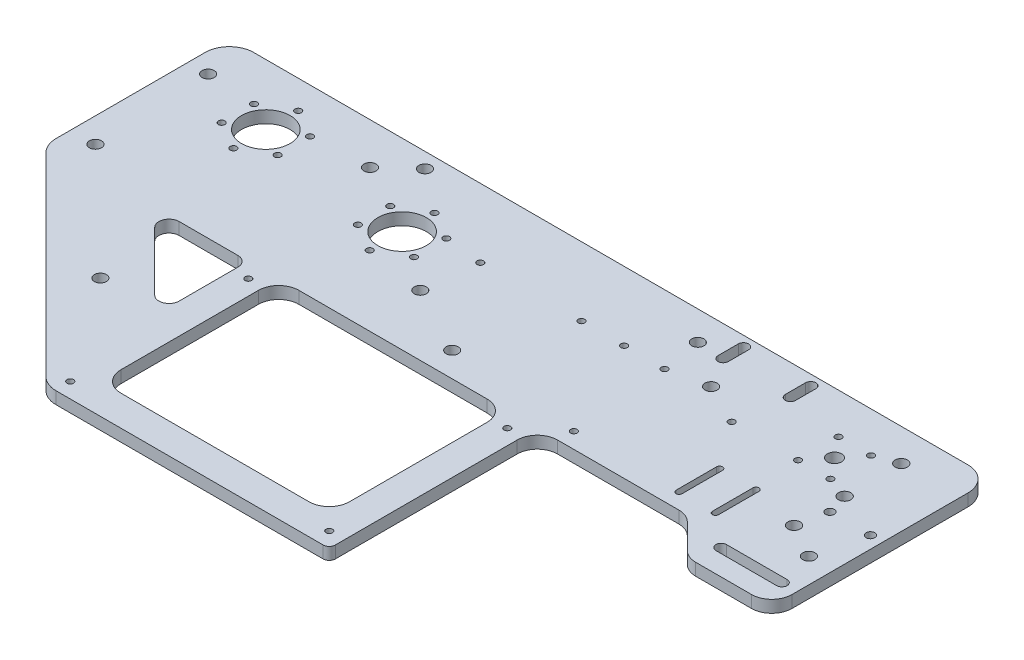
SolidWorks part; units mm, degrees
material "Policarbonato"
ref_plane "Plano frontal" through (0, 0, 0) normal (0, 0, 1) x (1, 0, 0)
ref_plane "Plano superior" through (0, 0, 0) normal (0, 1, 0) x (1, 0, 0)
ref_plane "Plano direito" through (0, 0, 0) normal (1, 0, 0) x (0, 0, -1)
sketch "Esboço1" plane through (0, 0, 0) normal (0, 1, 0) x (1, 0, 0)
  line L3 (-80.5574, -153.6487) -> (51.4721, -153.6487)
  line L4 (54.4721, -150.6487) -> (54.4721, -60.7886)
  line L6 (188.5279, -40.7886) -> (188.5279, 28)
  line L7 (176.5279, 40) -> (-176.5279, 40)
  line L8 (-188.5279, 28) -> (-188.5279, -45.6781)
  line L12 (-122.5768, -50.7886) -> (-93.5279, -50.7886)
  line L13 (-88.5279, -55.7886) -> (-88.5279, -84.8375)
  line L14 (-97.0635, -88.373) -> (-126.1124, -59.3241)
  line L15 (39.4721, -60.6487) -> (39.4721, -128.6487)
  line L16 (29.4721, -138.6487) -> (-63.5279, -138.6487)
  line L17 (-73.5279, -128.6487) -> (-73.5279, -60.6487)
  line L18 (-63.5279, -50.6487) -> (29.4721, -50.6487)
  line L20 (132.5279, 0) -> (148.5279, 0) construction
  line L21 (132.5279, 0) -> (132.5279, 20) construction
  line L22 (132.5279, 20) -> (148.5279, 20) construction
  line L23 (148.5279, 0) -> (148.5279, 20) construction
  line L24 (132.5279, 0) -> (148.5279, 20) construction
  line L25 (132.5279, 20) -> (148.5279, 0) construction
  line L30 (64.4721, -50.7886) -> (178.5279, -50.7886)
  line L31 (134.7221, -43) -> (134.7221, -23) construction
  line L32 (133.2221, -43) -> (133.2221, -23)
  line L33 (136.2221, -43) -> (136.2221, -23)
  line L34 (125.7221, -45.2211) -> (125.7221, -21.4375) construction
  line L36 (116.7221, -43) -> (116.7221, -23) construction
  line L37 (118.2221, -43) -> (118.2221, -23)
  line L38 (115.2221, -43) -> (115.2221, -23)
  line L39 (64.7221, -43) -> (134.7221, -43) construction
  line L40 (54.4721, -120.5) -> (144.9721, -120.5) construction
  line L41 (54.4721, -120.5) -> (54.4721, -7) construction
  line L42 (54.4721, -7) -> (144.9721, -7) construction
  line L43 (144.9721, -120.5) -> (144.9721, -7) construction
  line L44 (54.4721, -120.5) -> (144.9721, -7) construction
  line L45 (54.4721, -7) -> (144.9721, -120.5) construction
  line L46 (70.5279, 25) -> (70.5279, 35) construction
  line L47 (67.9779, 25) -> (67.9779, 35)
  line L48 (73.0779, 25) -> (73.0779, 35)
  line L49 (103.7779, 25) -> (103.7779, 35) construction
  line L50 (101.2279, 25) -> (101.2279, 35)
  line L51 (106.3279, 25) -> (106.3279, 35)
  line L52 (-185.0132, -54.1634) -> (-89.0426, -150.134)
  circle A0 centre (-81.0279, -58.1487) radius 1.6
  circle A1 centre (-81.0279, -146.1487) radius 1.6
  circle A2 centre (46.9721, -58.1487) radius 1.6
  circle A3 centre (46.9721, -146.1487) radius 1.6
  circle A8 centre (176.311, -38.4318) radius 3
  circle A9 centre (0, -38.4318) radius 3
  circle A11 centre (-140.5279, 10) radius 12
  circle A20 centre (-140.5279, 10) radius 16 construction
  circle A21 centre (-140.5279, -6) radius 1.6
  circle A22 centre (-154.3843, 2) radius 1.6
  circle A23 centre (-154.3843, 18) radius 1.6
  circle A24 centre (-84.3674, 32.5) radius 3
  circle A25 centre (-176.311, -38.4318) radius 3
  circle A26 centre (140.5279, 10) radius 3.5
  circle A27 centre (148.5279, 0) radius 1.6
  circle A28 centre (148.5279, 20) radius 1.6
  circle A29 centre (132.5279, 0) radius 1.6
  circle A30 centre (132.5279, 20) radius 1.6
  arc A31 (51.4721, -153.6487) -> (54.4721, -150.6487) centre (51.4721, -150.6487) ccw
  arc A34 (188.5279, 28) -> (176.5279, 40) centre (176.5279, 28) ccw
  arc A35 (-176.5279, 40) -> (-188.5279, 28) centre (-176.5279, 28) ccw
  arc A39 (-93.5279, -50.7886) -> (-88.5279, -55.7886) centre (-93.5279, -55.7886) cw
  arc A40 (-88.5279, -84.8375) -> (-97.0635, -88.373) centre (-93.5279, -84.8375) cw
  arc A41 (-126.1124, -59.3241) -> (-122.5768, -50.7886) centre (-122.5768, -55.7886) cw
  arc A42 (39.4721, -128.6487) -> (29.4721, -138.6487) centre (29.4721, -128.6487) cw
  arc A43 (-63.5279, -138.6487) -> (-73.5279, -128.6487) centre (-63.5279, -128.6487) cw
  arc A44 (-73.5279, -60.6487) -> (-63.5279, -50.6487) centre (-63.5279, -60.6487) cw
  arc A45 (29.4721, -50.6487) -> (39.4721, -60.6487) centre (29.4721, -60.6487) cw
  circle A46 centre (-140.5279, 26) radius 1.6
  circle A47 centre (-126.6715, 18) radius 1.6
  circle A48 centre (-126.6715, 2) radius 1.6
  circle A49 centre (-63.1716, 0) radius 16 construction
  circle A50 centre (-63.1716, -16) radius 1.6
  circle A51 centre (-77.028, -8) radius 1.6
  circle A52 centre (-77.028, 8) radius 1.6
  circle A53 centre (-63.1716, 16) radius 1.6
  circle A54 centre (-49.3152, 8) radius 1.6
  circle A55 centre (-49.3152, -8) radius 1.6
  circle A56 centre (-63.1716, 0) radius 12
  circle A57 centre (-33.5279, -20.6487) radius 3
  circle A58 centre (79.5279, 10) radius 3
  arc A62 (188.5279, -40.7886) -> (178.5279, -50.7886) centre (178.5279, -40.7886) cw
  arc A63 (54.4721, -60.7886) -> (64.4721, -50.7886) centre (64.4721, -60.7886) cw
  arc A64 (133.2221, -43) -> (136.2221, -43) centre (134.7221, -43) ccw
  arc A65 (136.2221, -23) -> (133.2221, -23) centre (134.7221, -23) ccw
  arc A66 (118.2221, -43) -> (115.2221, -43) centre (116.7221, -43) cw
  arc A67 (115.2221, -23) -> (118.2221, -23) centre (116.7221, -23) cw
  circle A68 centre (99.7221, 0) radius 1.6
  circle A69 centre (64.7221, -43) radius 1.6
  circle A70 centre (134.7221, -43) radius 1.6 construction
  circle A71 centre (-30.5279, 6) radius 1.6
  circle A72 centre (19.4721, 6) radius 1.6
  circle A73 centre (60.5279, 6) radius 1.6
  circle A75 centre (40.5279, 6) radius 1.6
  circle A76 centre (70.5279, 30) radius 2.55 construction
  circle A77 centre (103.7779, 30) radius 2.55 construction
  circle A78 centre (159.4679, 24.07) radius 3.05
  circle A79 centre (159.4679, -3.93) radius 3.05
  circle A80 centre (159.4679, -28.93) radius 3.05
  arc A81 (67.9779, 25) -> (73.0779, 25) centre (70.5279, 25) ccw
  arc A82 (73.0779, 35) -> (67.9779, 35) centre (70.5279, 35) ccw
  arc A83 (101.2279, 25) -> (106.3279, 25) centre (103.7779, 25) ccw
  arc A84 (106.3279, 35) -> (101.2279, 35) centre (103.7779, 35) ccw
  circle A85 centre (-178.5279, 19.5) radius 3
  circle A86 centre (-98.5279, 19.5) radius 3
  arc A87 (-80.5574, -153.6487) -> (-89.0426, -150.134) centre (-80.5574, -141.6487) cw
  arc A88 (-185.0132, -54.1634) -> (-188.5279, -45.6781) centre (-176.5279, -45.6781) cw
  circle A89 centre (57.3279, 25.68) radius 3
  point P14 (134.7221, -33)
  point P43 (-140.5279, 10)
  point P70 (-144.4721, -50.6487)
  point P82 (-85.5279, -153.6487)
  point P116 (-63.1716, 0)
  point P123 (0, 40)
  point P124 (116.7221, -33)
  point P129 (99.7221, -63.75)
  point P135 (99.7221, -7)
  point P141 (99.7221, -43)
  point P161 (70.5279, 30)
  point P168 (103.7779, 30)
  dimension "D2" = 3
  dimension "D8" = 12
  dimension "D10" = 12
  dimension "D11" = 61
  dimension "D12" = 203.9448
  dimension "D13" = 7.5
  dimension "D14" = 104.1605
  dimension "D16" = 135.7229
  dimension "D20" = 19.68
  dimension "D21" = 3.2
  dimension "D22" = 48.4318
  dimension "D23" = 32
  dimension "D24" = 3.2
  dimension "D25" = 6
  dimension "D26" = 24
  dimension "D27" = 48
  dimension "D28" = 30
  dimension "D29" = 40
  dimension "D30" = 6
  dimension "D34" = 30
  dimension "D31" = 32
  dimension "D32" = 3.2
  dimension "D33" = 24
  dimension "D35" = 6
  dimension "D36" = 155
  dimension "D37" = 30
  dimension "D44" = 7
  dimension "D48" = 10
  dimension "D6" = 10
  dimension "D58" = 5
  dimension "D62" = 1.5
  dimension "D68" = 70
  dimension "D72" = 80
  dimension "D75" = 5.1
  dimension "D80" = 14.07
  dimension "D82" = 6.1
  dimension "D83" = 10
  dimension "D19" = 6
  dimension "D1" = 137
  dimension "D9" = 377.0558
  dimension "D15" = 225
  dimension "D17" = 38
  dimension "D18" = 15
  dimension "D38" = 48
  dimension "D39" = 15
  dimension "D40" = 12.2169
  dimension "D41" = 12.2169
  dimension "D42" = 16
  dimension "D43" = 20
  dimension "D45" = 15
  dimension "D46" = 15
  dimension "D49" = 7.5
  dimension "D50" = 7.5
  dimension "D51" = 88
  dimension "D52" = 128
  dimension "D53" = 93
  dimension "D56" = 20.6487
  dimension "D57" = 68
  dimension "D59" = 10
  dimension "D60" = 20.5
  dimension "D61" = 20
  dimension "D63" = 9
  dimension "D64" = 113.5
  dimension "D65" = 90.5
  dimension "D66" = 7
  dimension "D67" = 43
  dimension "D69" = 34
  dimension "D70" = 110
  dimension "D71" = 50
  dimension "D73" = 20
  dimension "D74" = 33.25
  dimension "D76" = 10
  dimension "D77" = 10
  dimension "D78" = 25
  dimension "D79" = 28
  dimension "D81" = 18.94
  dimension "D84" = 80
extrude "Ressalto-extrusão1" add sketch "Esboço1" against normal blind 6
sketch "Esboço2" plane through (0, 0, 0) normal (0, 1, 0) x (1, 0, 0)
  line L0 (188.5279, -40.7886) -> (188.5279, 28) construction
  line L1 (-126.1124, -59.3241) -> (-97.0635, -88.373) construction
  line L2 (-131.2731, -107.9035) -> (-104.403, -81.0335) construction
  line L3 (-185.0132, -54.1634) -> (-89.0426, -150.134) construction
  line L4 (134.7221, -21.5) -> (134.7221, -6.98) construction
  circle A1 centre (-117.8381, -94.4685) radius 3
  arc A2 (-188.5279, -45.6781) -> (-185.0132, -54.1634) centre (-176.5279, -45.6781) ccw construction
  circle A3 centre (182.5279, -14.24) radius 2.15
  circle A4 centre (162.5279, -14.24) radius 2.15
  arc A5 (136.2221, -23) -> (133.2221, -23) centre (134.7221, -23) ccw construction
  circle A6 centre (159.4679, -3.93) radius 3.05 construction
  point P1 (-117.8381, -94.4685)
  point P25 (159.4679, -6.98)
  point P26 (134.7221, -14.24)
  point P31 (159.4679, -3.93)
  dimension "D1" = 76
  dimension "D2" = 6
  dimension "D3" = 20
  dimension "D4" = 4.3
  dimension "D5" = 6
extrude "Corte-extrusão1" cut sketch "Esboço2" against normal blind 10
sketch "Esboço3" plane through (0, 0, 0) normal (0, 1, 0) x (1, 0, 0)
  line L0 (146.7858, -68.9886) -> (118.5858, -40.7886)
  line L1 (188.5279, -40.7886) -> (146.7858, -40.7886)
  line L2 (188.5279, -40.7886) -> (188.5279, -68.9886)
  line L3 (188.5279, -68.9886) -> (146.7858, -68.9886)
  line L4 (146.7858, -40.7886) -> (146.7858, -68.9886)
  line L5 (118.5858, -40.7886) -> (146.7858, -40.7886)
  line L6 (180.9279, -56.3886) -> (150.9279, -56.3886) construction
  line L7 (180.9279, -58.9886) -> (150.9279, -58.9886)
  line L8 (180.9279, -53.7886) -> (150.9279, -53.7886)
  line L10 (133.2221, -23) -> (133.2221, -43) construction
  line L11 (136.2221, -43) -> (136.2221, -23) construction
  line L12 (133.2221, -23) -> (133.2221, -43)
  line L13 (136.2221, -43) -> (136.2221, -23)
  line L14 (115.2221, -23) -> (115.2221, -43) construction
  line L15 (118.2221, -43) -> (118.2221, -23) construction
  line L16 (115.2221, -23) -> (115.2221, -43)
  line L17 (118.2221, -43) -> (118.2221, -23)
  line L18 (64.4721, -50.7886) -> (178.5279, -50.7886) construction
  arc A0 (180.9279, -58.9886) -> (180.9279, -53.7886) centre (180.9279, -56.3886) ccw
  arc A1 (150.9279, -53.7886) -> (150.9279, -58.9886) centre (150.9279, -56.3886) ccw
  circle A2 centre (176.311, -38.4318) radius 3 construction
  arc A3 (133.2221, -43) -> (136.2221, -43) centre (134.7221, -43) ccw construction
  circle A4 centre (176.311, -38.4318) radius 3
  arc A5 (133.2221, -43) -> (136.2221, -43) centre (134.7221, -43) ccw
  arc A6 (115.2221, -43) -> (118.2221, -43) centre (116.7221, -43) ccw construction
  arc A7 (115.2221, -43) -> (118.2221, -43) centre (116.7221, -43) ccw
  point P8 (165.9279, -56.3886)
  point P13 (183.5279, -56.3886)
  point P14 (150.9279, -54.277)
  point P16 (148.3279, -56.3886)
  point P30 (0, 0)
  dimension "D3" = 2.6
  dimension "D1" = 45
  dimension "D2" = 30
  dimension "D4" = 10
  dimension "D5" = 10
  dimension "D6" = 5
  dimension "D7" = 3
extrude "Ressalto-extrusão2" add sketch "Esboço3" against normal up to surface (6 mm away) contours L5 L0 L4 | L1 L4 L3 L2 A1 L8 A0 L7 region at (147.2895, 0, 54.8886) region at (137.4557, 0, 50.3904) up to face at (-117.8381, -6, 91.4685)
fillet "Filete1" radius 10 3 edges at (188.5279, -3, 68.9886) (146.7858, -3, 68.9886) (128.5858, -3, 50.7886)
